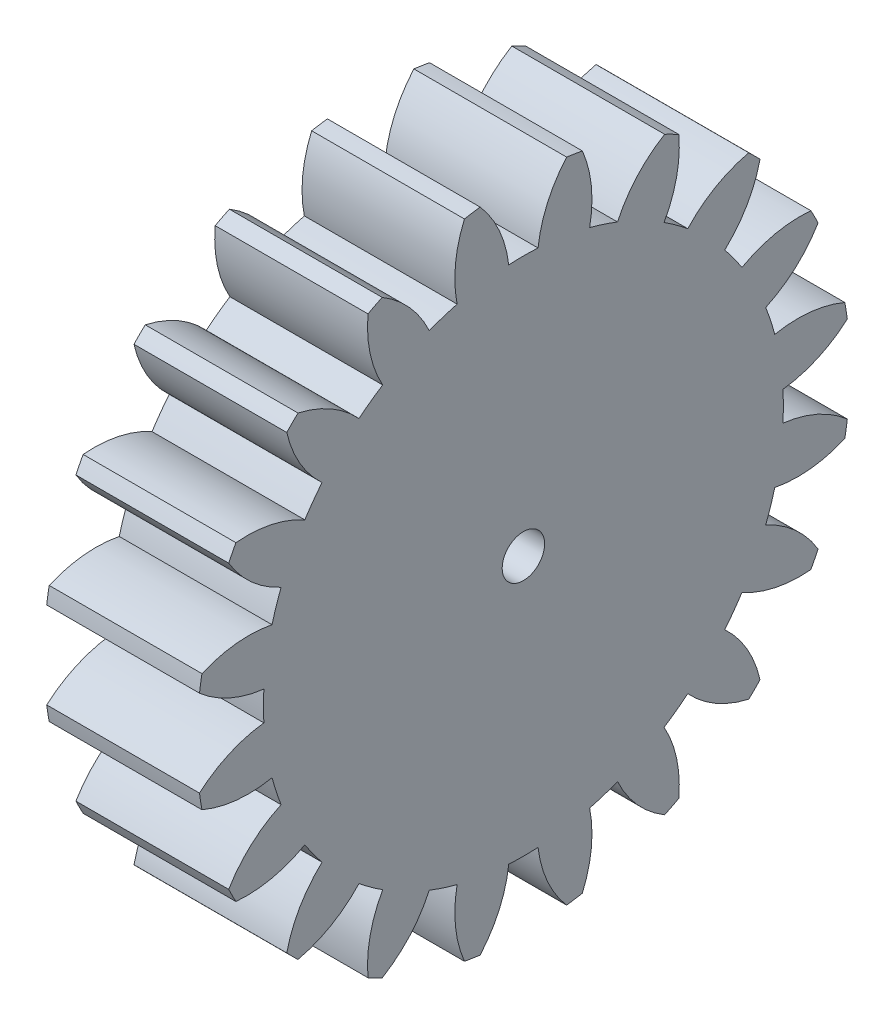
SolidWorks part; units mm, degrees
ref_plane "Plane1" through (0, 0, 0) normal (0, 0, 1) x (1, 0, 0)
ref_plane "Plane2" through (0, 0, 0) normal (0, 1, 0) x (1, 0, 0)
ref_plane "Plane3" through (0, 0, 0) normal (1, 0, 0) x (0, 0, -1)
other "Configuration Table"
sketch "HoldingSke" plane through (0, 0, 0) normal (0, 1, 0) x (1, 0, 0)
  line L0 (0, 0) -> (0.2685, -0.0977)
  line L1 (-15, 0) -> (100, 0) construction
  line L2 (0, 0) -> (-2.1039, 2.3779)
  line L3 (0, 0) -> (-11.863, 4.5341)
  line L4 (0, 0) -> (8.1152, 2.9537)
  line L5 (0, 0) -> (-46.8476, -17.4728)
  line L6 (0, 0) -> (-14.9213, -10.0675)
  line L7 (-2.1039, 2.3779) -> (8.6586, 51.2059)
  line L8 (-76.2, 54.61) -> (-75.3, 54.61)
  line L9 (-71.009, 38.7566) -> (-53.1078, 45.2721)
  line L10 (-76.2, 71.12) -> (104.1128, 71.12)
  line L11 (0, 0) -> (-18, 0)
  line L12 (-76.2, 101.6) -> (-76.083, 101.6)
  line L13 (24.9733, 27.94) -> (52.9518, 28.4284)
  line L14 (24.9733, 27.94) -> (24.9743, 27.94)
  line L15 (24.9733, 27.94) -> (100.4006, 29.5858)
  line L16 (-63.627, -3.5) -> (-12.827, -3.5)
  circle A0 centre (0, 0) radius 2.5
  circle A1 centre (0, 0) radius 30.624
  circle A2 centre (0, 0) radius 37.5
  circle A3 centre (0, 0) radius 2.5
  dimension "Num_teeth" = 20
  dimension "Pitch_radius" = 180.3128
  dimension "Width" = 18
  dimension "Thickness" = 18
sketch "BasProSke" plane through (0, 0, 0) normal (0, 1, 0) x (1, 0, 0)
  line L0 (-10, 0) -> (60, 0) construction
  line L1 (0, 0) -> (0, 38.5)
  line L2 (0, 0) -> (18, 0)
  line L3 (18, 0) -> (18, 38.5)
  line L4 (18, 38.5) -> (0, 38.5)
  dimension "Thickness" = 18
  dimension "Diameter" = 77
revolve "Base-Revolve" add sketch "BasProSke" angle 360 about L0
sketch "TooCutSke" plane through (0, 0, 0) normal (1, 0, 0) x (0, 0, -1)
  line L1 (0, 0) -> (0, 107) construction
  line L2 (0, 0) -> (-2.9507, 34.8754) construction
  line L3 (0, 0) -> (-10.9215, 68.9557) construction
  line L4 (-2.9507, 34.8754) -> (-5.4608, 34.4778) construction
  arc A0 (1.7255, 30.5753) -> (-1.7255, 30.5753) centre (0, 0) ccw
  arc A1 (5.1169, 38.1841) -> (-5.1169, 38.1841) centre (0, 0) ccw
  circle A2 centre (0, 0) radius 35 construction
  circle A3 centre (0, 0) radius 32.8892 construction
  arc A4 (-1.7255, 30.5753) -> (-5.1169, 38.1841) centre (-15.6295, 28.9382) ccw
  arc A5 (5.1169, 38.1841) -> (1.7255, 30.5753) centre (15.6295, 28.9382) ccw
extrude "ToothCut" cut sketch "TooCutSke" along normal through all
fillet "Breaks" [suppressed] radius 0.07 tangent propagation no
fillet "RootFillets" [suppressed] radius 0.876
pattern_circular "TeethCuts" count 20 every 18 about axis through (-10, 0, 0) along (1, 0, 0) of "ToothCut", "RootFillets", "Breaks"
sketch "HubNeaOneSke" plane through (0, 0, 0) normal (-1, 0, 0) x (0, 0, 1)
  circle A0 centre (0, 0) radius 30.624
  dimension "Diameter" = 61.248
extrude "HubNearOne" [suppressed] add sketch "HubNeaOneSke" along normal blind 32.0001
sketch "HubNeaBotSke" plane through (0, 0, 0) normal (-1, 0, 0) x (0, 0, 1)
  circle A0 centre (0, 0) radius 30.624
  dimension "Diameter" = 61.248
extrude "HubNearBoth" [suppressed] add sketch "HubNeaBotSke" along normal blind 16
ref_plane "FarPln" through (18, 0, 0) normal (1, 0, 0) x (0, 0, -1)
sketch "HubFarSke" plane through (18, 0, 0) normal (1, 0, 0) x (0, 0, -1)
  circle A0 centre (0, 0) radius 30.624
  dimension "Diameter" = 61.248
extrude "HubFar" [suppressed] add sketch "HubFarSke" along normal blind 16
sketch "BorSke" plane through (0, 0, 0) normal (1, 0, 0) x (0, 0, -1)
  circle A0 centre (0, 0) radius 2.5
  dimension "Diameter" = 5
extrude "Bore" cut sketch "BorSke" along normal mid plane 100.0001
sketch "KeySke" plane through (0, 0, 0) normal (1, 0, 0) x (0, 0, -1)
  line L0 (-1, 0) -> (-1, 3.4)
  line L1 (-1, 3.4) -> (1, 3.4)
  line L2 (1, 3.4) -> (1, 0)
  line L3 (0, 0) -> (0, 34) construction
  line L4 (-1, 0) -> (1, 0)
extrude "Keyway" [suppressed] cut sketch "KeySke" along normal mid plane 100.0001
pattern_circular "Keyway2" [suppressed] count 2 every 90 about axis through (-10, 0, 0) along (1, 0, 0)
equation "' \"Module@HoldingSke\" = 6.35"
equation "' \"Num_teeth@HoldingSke\" = 12"
equation "' \"Ap@HoldingSke\" =  20"
equation "' \"Ap@HoldingSke\" = 20"
equation "' \"Width@HoldingSke\" = 0.5 * 25.4"
equation "' \"Hub_dia@HoldingSke\"= 1 * 25.4"
equation "' \"Hub_dia@HoldingSke\" = 1 * 25.4"
equation "' \"Overall_len@HoldingSke\" = 1.0 * 25.4"
equation "' \"Bore@HoldingSke\" = 0.75 * 25.4"
equation "' \"T_dim@HoldingSke\" = 0.1 * 25.4"
equation "' \"Width@KeySke\" = 0.25 * 25.4"
equation "' \"Show_teeth@HoldingSke\" = 13"
equation "' \"Backlash@HoldingSke\" = 0.009 * 25.4"
equation "' \"Addendum_fac@HoldingSke\" = 1.0"
equation "' \"Dedendum_fac@HoldingSke\" = 1.25"
equation "' \"Dedendum_add@HoldingSke\" = 0.00005 * 25.4"
equation "' \"Clearance_fac@HoldingSke\" = 0.25"
equation "\"Pitch@HoldingSke\" = 1 / \"Module@HoldingSke\""
equation "\"Overcut_dia@TooCutSke\" = (\"Num_teeth@HoldingSke\" + 2 * \"Addendum_fac@HoldingSke\") / \"Pitch@HoldingSke\" + 0.002 * 25.4"
equation "\"Pitch_dia@TooCutSke\" = \"Num_teeth@HoldingSke\" / \"Pitch@HoldingSke\""
equation "\"Base_dia@TooCutSke\" = \"Num_teeth@HoldingSke\" / \"Pitch@HoldingSke\" * cos((\"Ap@HoldingSke\"  * 3.14159265 / 180))"
equation "\"Root_dia@TooCutSke\" = (\"Num_teeth@HoldingSke\" + 2) / \"Pitch@HoldingSke\" - 2 * (\"Addendum_fac@HoldingSke\" + \"Dedendum_fac@HoldingSke\") / \"Pitch@HoldingSke\" - \"Dedendum_add@HoldingSke\" * 2"
equation "\"Half_ang@TooCutSke\" = 180 / \"Num_teeth@HoldingSke\""
equation "\"Half_CT@TooCutSke\" = \"Num_teeth@HoldingSke\" / \"Pitch@HoldingSke\" * sin((3.14159265 / 2 / \"Num_teeth@HoldingSke\")) / 2 - 7 * \"Backlash@HoldingSke\" / 4"
equation "\"Flank_rad@TooCutSke\" = \"Num_teeth@HoldingSke\" / \"Pitch@HoldingSke\" / 5"
equation "\"Radius@RootFillets\" = \"Clearance_fac@HoldingSke\" / \"Pitch@HoldingSke\" + \"Dedendum_add@HoldingSke\""
equation "\"Break_rad@Breaks\" = 0.02 / \"Pitch@HoldingSke\""
equation "\"Thickness@HoldingSke\" = \"Width@HoldingSke\""
equation "\"OAL@HoldingSke\" = \"Thickness@HoldingSke\""
equation "\"MHD@HoldingSke\" = (\"Num_teeth@HoldingSke\" + 2) / \"Pitch@HoldingSke\" - 2 * (\"Addendum_fac@HoldingSke\" + \"Dedendum_fac@HoldingSke\")  / \"Pitch@HoldingSke\" - \"Dedendum_add@HoldingSke\" * 2"
equation "\"MBD@HoldingSke\" = (\"Num_teeth@HoldingSke\" + 2) / \"Pitch@HoldingSke\" - 2 * (\"Addendum_fac@HoldingSke\" + \"Dedendum_fac@HoldingSke\")  / \"Pitch@HoldingSke\" - \"Dedendum_add@HoldingSke\" * 2 - 0.002 * 25.4"
equation "\"MHD@HoldingSke\" = ((sgn( \"MHD@HoldingSke\" - \"Hub_dia@HoldingSke\" )-1)*( \"MHD@HoldingSke\" - \"Hub_dia@HoldingSke\" ))/-2+ \"Hub_dia@HoldingSke\""
equation "\"MBD@HoldingSke\" = ((sgn( \"MBD@HoldingSke\" - \"Bore@HoldingSke\" )-1)*( \"MBD@HoldingSke\" - \"Bore@HoldingSke\" ))/-2+ \"Bore@HoldingSke\""
equation "\"OAL@HoldingSke\" = ((sgn( \"OAL@HoldingSke\" - \"Overall_len@HoldingSke\" )+1)*( \"OAL@HoldingSke\" - \"Overall_len@HoldingSke\" ))/2 + \"Overall_len@HoldingSke\" + 0.000002 * 25.4"
equation "\"Num_teeth@TeethCuts\" = int( \"Show_teeth@HoldingSke\" ) + 1"
equation "\"Num_teeth@TeethCuts\" = ((sgn( \"Num_teeth@TeethCuts\" - \"Num_teeth@HoldingSke\" )-1)*( \"Num_teeth@TeethCuts\" - \"Num_teeth@HoldingSke\" ))/-2+ \"Num_teeth@HoldingSke\""
equation "\"Num_teeth@TeethCuts\" = ((sgn( \"Num_teeth@TeethCuts\" - 2.0)+1)*( \"Num_teeth@TeethCuts\" - 2.0))/2 +2.0"
equation "\"Angle@TeethCuts\" = 360.0 / \"Num_teeth@HoldingSke\""
equation "\"Diameter@BasProSke\" = (\"Num_teeth@HoldingSke\" + 2 * \"Addendum_fac@HoldingSke\") / \"Pitch@HoldingSke\""
equation "\"Thickness@BasProSke\"  = \"Thickness@HoldingSke\""
equation "' \"Fillet_rad@BasProSke\" =  \"Thickness@HoldingSke\" * 0.05"
equation "' \"Fillet_rad@BasProSke\" = \"Thickness@HoldingSke\" * 0.05"
equation "\"MHD@HoldingSke\" = ((sgn( \"MHD@HoldingSke\" - \"Root_dia@TooCutSke\" )-1)*( \"MHD@HoldingSke\" - \"Root_dia@TooCutSke\" ))/-2+ \"Root_dia@TooCutSke\""
equation "\"Diameter@HubNeaOneSke\" = \"MHD@HoldingSke\""
equation "\"Length@HubNearOne\" = \"OAL@HoldingSke\" - \"Thickness@BasProSke\""
equation "\"Diameter@HubNeaBotSke\" = \"MHD@HoldingSke\""
equation "\"Length@HubNearBoth\" = ( \"OAL@HoldingSke\" - \"Thickness@BasProSke\" ) / 2.0"
equation "\"Thickness@FarPln\" = \"Thickness@BasProSke\""
equation "\"Diameter@HubFarSke\" = \"MHD@HoldingSke\""
equation "\"Length@HubFar\" = ( \"OAL@HoldingSke\" - \"Thickness@BasProSke\" ) / 2.0"
equation "\"Diameter@BorSke\" = \"MBD@HoldingSke\""
equation "\"D1@Bore\" = \"OAL@HoldingSke\" * 2.0"
equation "\"D1@Keyway\" = \"OAL@HoldingSke\" * 2.0"
equation "\"Offset@KeySke\" = \"T_dim@HoldingSke\" + \"MBD@HoldingSke\" / 2.0"
